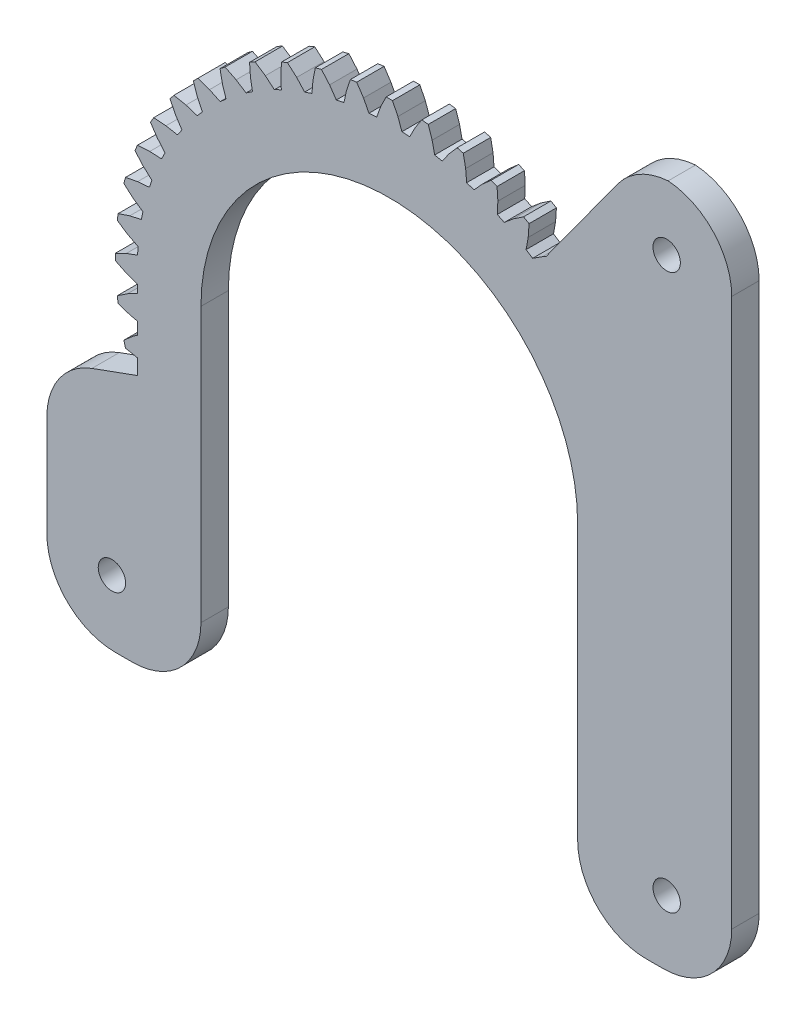
SolidWorks part; units mm, degrees
material "Delrin 2700 NC010, Low Viscosity Acetal Copolymer (SS)"
ref_plane "Front Plane" through (0, 0, 0) normal (0, 0, 1) x (1, 0, 0)
ref_plane "Top Plane" through (0, 0, 0) normal (0, 1, 0) x (1, 0, 0)
ref_plane "Right Plane" through (0, 0, 0) normal (1, 0, 0) x (0, 0, -1)
sketch "Sketch1" plane through (0, 0, 0) normal (0, 0, 1) x (1, 0, 0)
  line L0 (83.8835, 67.191) -> (85.5092, 66.6061)
  line L1 (85.5092, 66.6061) -> (87.1271, 65.8138)
  line L2 (87.1271, 65.8138) -> (87.1271, 64.8854)
  line L3 (87.1271, 64.8854) -> (85.5092, 64.0931)
  line L4 (85.5092, 64.0931) -> (83.8835, 63.5083)
  line L5 (83.8835, 63.5083) -> (83.8095, 62.3776)
  line L6 (83.8095, 62.3776) -> (85.3448, 61.5855)
  line L7 (85.3448, 61.5855) -> (86.8456, 60.5888)
  line L8 (86.8456, 60.5888) -> (86.7243, 59.6683)
  line L9 (86.7243, 59.6683) -> (85.0168, 59.094)
  line L10 (85.0168, 59.094) -> (83.3288, 58.7263)
  line L11 (83.3288, 58.7263) -> (83.1077, 57.615)
  line L12 (83.1077, 57.615) -> (84.5266, 56.6293)
  line L13 (84.5266, 56.6293) -> (85.8844, 55.4453)
  line L14 (85.8844, 55.4453) -> (85.6441, 54.5485)
  line L15 (85.6441, 54.5485) -> (83.8761, 54.202)
  line L16 (83.8761, 54.202) -> (82.1545, 54.0577)
  line L17 (82.1545, 54.0577) -> (81.7903, 52.9848)
  line L18 (81.7903, 52.9848) -> (83.0684, 51.8222)
  line L19 (83.0684, 51.8222) -> (84.26, 50.4711)
  line L20 (84.26, 50.4711) -> (83.9048, 49.6134)
  line L21 (83.9048, 49.6134) -> (82.1066, 49.5006)
  line L22 (82.1066, 49.5006) -> (80.3809, 49.5823)
  line L23 (80.3809, 49.5823) -> (79.8799, 48.5661)
  line L24 (79.8799, 48.5661) -> (80.9952, 47.2468)
  line L25 (80.9952, 47.2468) -> (82.0003, 45.7516)
  line L26 (82.0003, 45.7516) -> (81.5361, 44.9476)
  line L27 (81.5361, 44.9476) -> (79.7387, 45.0704)
  line L28 (79.7387, 45.0704) -> (78.0384, 45.3766)
  line L29 (78.0384, 45.3766) -> (77.4089, 44.4346)
  line L30 (77.4089, 44.4346) -> (78.3426, 42.9809)
  line L31 (78.3426, 42.9809) -> (79.1439, 41.3674)
  line L32 (79.1439, 41.3674) -> (78.5788, 40.6309)
  line L33 (78.5788, 40.6309) -> (76.8128, 40.9873)
  line L34 (76.8128, 40.9873) -> (75.167, 41.5128)
  line L35 (75.167, 41.5128) -> (74.4199, 40.6609)
  line L36 (74.4199, 40.6609) -> (75.1558, 39.0979)
  line L37 (75.1558, 39.0979) -> (75.7397, 37.3936)
  line L38 (75.7397, 37.3936) -> (75.0832, 36.737)
  line L39 (75.0832, 36.737) -> (73.3788, 37.3209)
  line L40 (73.3788, 37.3209) -> (71.8158, 38.0569)
  line L41 (71.8158, 38.0569) -> (70.9639, 37.3097)
  line L42 (70.9639, 37.3097) -> (71.4895, 35.6639)
  line L43 (71.4895, 35.6639) -> (71.8459, 33.898)
  line L44 (71.8459, 33.898) -> (71.1093, 33.3328)
  line L45 (71.1093, 33.3328) -> (69.4958, 34.1341)
  line L46 (69.4958, 34.1341) -> (68.0421, 35.0679)
  line L47 (68.0421, 35.0679) -> (67.1001, 34.4384)
  line L48 (67.1001, 34.4384) -> (67.4064, 32.738)
  line L49 (67.4064, 32.738) -> (67.5292, 30.9407)
  line L50 (67.5292, 30.9407) -> (66.7251, 30.4764)
  line L51 (66.7251, 30.4764) -> (65.23, 31.4815)
  line L52 (65.23, 31.4815) -> (63.9107, 32.5969)
  line L53 (63.9107, 32.5969) -> (62.8945, 32.0958)
  line L54 (62.8945, 32.0958) -> (62.9762, 30.3701)
  line L55 (62.9762, 30.3701) -> (62.8633, 28.572)
  line L56 (62.8633, 28.572) -> (62.0056, 28.2167)
  line L57 (62.0056, 28.2167) -> (60.6545, 29.4083)
  line L58 (60.6545, 29.4083) -> (59.4919, 30.6864)
  line L59 (59.4919, 30.6864) -> (58.419, 30.3222)
  line L60 (58.419, 30.3222) -> (58.2748, 28.6006)
  line L61 (58.2748, 28.6006) -> (57.9283, 26.8327)
  line L62 (57.9283, 26.8327) -> (57.0315, 26.5924)
  line L63 (57.0315, 26.5924) -> (55.8474, 27.9502)
  line L64 (55.8474, 27.9502) -> (54.8618, 29.369)
  line L65 (54.8618, 29.369) -> (53.7504, 29.1479)
  line L66 (53.7504, 29.1479) -> (53.3827, 27.4599)
  line L67 (53.3827, 27.4599) -> (52.8084, 25.7524)
  line L68 (52.8084, 25.7524) -> (51.888, 25.6311)
  line L69 (51.888, 25.6311) -> (50.8913, 27.1319)
  line L70 (50.8913, 27.1319) -> (50.0992, 28.6672)
  line L71 (50.0992, 28.6672) -> (48.9685, 28.5932)
  line L72 (48.9685, 28.5932) -> (48.3836, 26.9675)
  line L73 (48.3836, 26.9675) -> (47.5914, 25.3496)
  line L74 (47.5914, 25.3496) -> (46.6629, 25.3496)
  line L75 (46.6629, 25.3496) -> (45.8707, 26.9675)
  line L76 (45.8707, 26.9675) -> (45.2858, 28.5932)
  line L77 (45.2858, 28.5932) -> (44.1551, 28.6672)
  line L78 (44.1551, 28.6672) -> (43.363, 27.1319)
  line L79 (43.363, 27.1319) -> (42.3663, 25.6311)
  line L80 (42.3663, 25.6311) -> (41.4459, 25.7524)
  line L81 (41.4459, 25.7524) -> (40.8715, 27.4599)
  line L82 (40.8715, 27.4599) -> (40.5038, 29.1479)
  line L83 (40.5038, 29.1479) -> (39.3925, 29.369)
  line L84 (39.3925, 29.369) -> (38.4068, 27.9502)
  line L85 (38.4068, 27.9502) -> (37.2228, 26.5924)
  line L86 (37.2228, 26.5924) -> (36.326, 26.8327)
  line L87 (36.326, 26.8327) -> (35.9795, 28.6006)
  line L88 (35.9795, 28.6006) -> (35.8352, 30.3222)
  line L89 (35.8352, 30.3222) -> (34.7624, 30.6864)
  line L90 (34.7624, 30.6864) -> (33.5998, 29.4083)
  line L91 (33.5998, 29.4083) -> (32.2487, 28.2167)
  line L92 (32.2487, 28.2167) -> (31.3909, 28.572)
  line L93 (31.3909, 28.572) -> (31.2781, 30.3701)
  line L94 (31.2781, 30.3701) -> (31.3598, 32.0958)
  line L95 (31.3598, 32.0958) -> (30.3436, 32.5969)
  line L96 (30.3436, 32.5969) -> (29.0243, 31.4815)
  line L97 (29.0243, 31.4815) -> (27.5292, 30.4764)
  line L98 (27.5292, 30.4764) -> (26.7251, 30.9407)
  line L99 (26.7251, 30.9407) -> (26.8479, 32.738)
  line L100 (26.8479, 32.738) -> (27.1541, 34.4384)
  line L101 (27.1541, 34.4384) -> (26.2121, 35.0679)
  line L102 (26.2121, 35.0679) -> (24.7585, 34.1341)
  line L103 (24.7585, 34.1341) -> (23.1449, 33.3328)
  line L104 (23.1449, 33.3328) -> (22.4084, 33.898)
  line L105 (22.4084, 33.898) -> (22.7648, 35.6639)
  line L106 (22.7648, 35.6639) -> (23.2904, 37.3097)
  line L107 (23.2904, 37.3097) -> (22.4384, 38.0569)
  line L108 (22.4384, 38.0569) -> (20.8754, 37.3209)
  line L109 (20.8754, 37.3209) -> (19.1711, 36.737)
  line L110 (19.1711, 36.737) -> (18.5146, 37.3936)
  line L111 (18.5146, 37.3936) -> (19.0984, 39.0979)
  line L112 (19.0984, 39.0979) -> (19.8344, 40.6609)
  line L113 (19.8344, 40.6609) -> (19.0872, 41.5128)
  line L114 (19.0872, 41.5128) -> (17.4414, 40.9873)
  line L115 (17.4414, 40.9873) -> (15.6755, 40.6309)
  line L116 (15.6755, 40.6309) -> (15.1103, 41.3674)
  line L117 (15.1103, 41.3674) -> (15.9116, 42.9809)
  line L118 (15.9116, 42.9809) -> (16.8454, 44.4346)
  line L119 (16.8454, 44.4346) -> (16.2159, 45.3766)
  line L120 (16.2159, 45.3766) -> (14.5155, 45.0704)
  line L121 (14.5155, 45.0704) -> (12.7182, 44.9476)
  line L122 (12.7182, 44.9476) -> (12.2539, 45.7516)
  line L123 (12.2539, 45.7516) -> (13.2591, 47.2468)
  line L124 (13.2591, 47.2468) -> (14.3744, 48.5661)
  line L125 (14.3744, 48.5661) -> (13.8733, 49.5823)
  line L126 (13.8733, 49.5823) -> (12.1476, 49.5006)
  line L127 (12.1476, 49.5006) -> (10.3495, 49.6134)
  line L128 (10.3495, 49.6134) -> (9.9942, 50.4711)
  line L129 (9.9942, 50.4711) -> (11.1858, 51.8222)
  line L130 (11.1858, 51.8222) -> (12.4639, 52.9848)
  line L131 (12.4639, 52.9848) -> (12.0997, 54.0577)
  line L132 (12.0997, 54.0577) -> (10.3781, 54.202)
  line L133 (10.3781, 54.202) -> (8.6102, 54.5485)
  line L134 (8.6102, 54.5485) -> (8.3699, 55.4453)
  line L135 (8.3699, 55.4453) -> (9.7277, 56.6293)
  line L136 (9.7277, 56.6293) -> (11.1465, 57.615)
  line L137 (11.1465, 57.615) -> (10.9255, 58.7263)
  line L138 (10.9255, 58.7263) -> (9.2374, 59.094)
  line L139 (9.2374, 59.094) -> (7.5299, 59.6683)
  line L140 (7.5299, 59.6683) -> (7.4086, 60.5888)
  line L141 (7.4086, 60.5888) -> (8.9094, 61.5855)
  line L142 (8.9094, 61.5855) -> (10.4448, 62.3776)
  line L143 (10.4448, 62.3776) -> (10.3707, 63.5083)
  line L144 (10.3707, 63.5083) -> (8.745, 64.0931)
  line L145 (8.745, 64.0931) -> (7.1271, 64.8854)
  line L146 (7.1271, 64.8854) -> (7.1271, 65.8138)
  line L147 (7.1271, 65.8138) -> (8.745, 66.6061)
  line L148 (8.745, 66.6061) -> (10.3707, 67.191)
  line L149 (10.3707, 67.191) -> (10.4448, 68.3216)
  line L150 (10.4448, 68.3216) -> (8.9094, 69.1138)
  line L151 (8.9094, 69.1138) -> (7.4086, 70.1105)
  line L152 (7.4086, 70.1105) -> (7.5299, 71.0309)
  line L153 (7.5299, 71.0309) -> (9.2374, 71.6052)
  line L154 (9.2374, 71.6052) -> (10.9255, 71.9729)
  line L155 (10.9255, 71.9729) -> (11.1465, 73.0842)
  line L156 (11.1465, 73.0842) -> (9.7277, 74.0699)
  line L157 (9.7277, 74.0699) -> (8.3699, 75.254)
  line L158 (8.3699, 75.254) -> (8.6102, 76.1508)
  line L159 (8.6102, 76.1508) -> (10.3781, 76.4973)
  line L160 (10.3781, 76.4973) -> (12.0997, 76.6415)
  line L161 (12.0997, 76.6415) -> (12.4639, 77.7144)
  line L162 (12.4639, 77.7144) -> (11.1858, 78.877)
  line L163 (11.1858, 78.877) -> (9.9942, 80.2281)
  line L164 (9.9942, 80.2281) -> (10.3495, 81.0858)
  line L165 (10.3495, 81.0858) -> (12.1476, 81.1987)
  line L166 (12.1476, 81.1987) -> (13.8733, 81.117)
  line L167 (13.8733, 81.117) -> (14.3744, 82.1332)
  line L168 (14.3744, 82.1332) -> (13.2591, 83.4525)
  line L169 (13.2591, 83.4525) -> (12.2539, 84.9476)
  line L170 (12.2539, 84.9476) -> (12.7182, 85.7516)
  line L171 (12.7182, 85.7516) -> (14.5155, 85.6289)
  line L172 (14.5155, 85.6289) -> (16.2159, 85.3226)
  line L173 (16.2159, 85.3226) -> (16.8454, 86.2646)
  line L174 (16.8454, 86.2646) -> (15.9116, 87.7183)
  line L175 (15.9116, 87.7183) -> (15.1103, 89.3318)
  line L176 (15.1103, 89.3318) -> (15.6755, 90.0684)
  line L177 (15.6755, 90.0684) -> (17.4414, 89.712)
  line L178 (17.4414, 89.712) -> (19.0872, 89.1864)
  line L179 (19.0872, 89.1864) -> (19.8344, 90.0383)
  line L180 (19.8344, 90.0383) -> (19.0984, 91.6013)
  line L181 (19.0984, 91.6013) -> (18.5146, 93.3057)
  line L182 (18.5146, 93.3057) -> (19.1711, 93.9622)
  line L183 (19.1711, 93.9622) -> (20.8754, 93.3783)
  line L184 (20.8754, 93.3783) -> (22.4384, 92.6424)
  line L185 (22.4384, 92.6424) -> (23.2904, 93.3895)
  line L186 (23.2904, 93.3895) -> (22.7648, 95.0353)
  line L187 (22.7648, 95.0353) -> (22.4084, 96.8013)
  line L188 (22.4084, 96.8013) -> (23.1449, 97.3664)
  line L189 (23.1449, 97.3664) -> (24.7585, 96.5651)
  line L190 (24.7585, 96.5651) -> (26.2121, 95.6314)
  line L191 (26.2121, 95.6314) -> (27.1541, 96.2609)
  line L192 (27.1541, 96.2609) -> (26.8479, 97.9612)
  line L193 (26.8479, 97.9612) -> (26.7251, 99.7586)
  line L194 (26.7251, 99.7586) -> (27.5292, 100.2228)
  line L195 (27.5292, 100.2228) -> (29.0243, 99.2177)
  line L196 (29.0243, 99.2177) -> (30.3436, 98.1023)
  line L197 (30.3436, 98.1023) -> (31.3598, 98.6034)
  line L198 (31.3598, 98.6034) -> (31.2781, 100.3291)
  line L199 (31.2781, 100.3291) -> (31.3909, 102.1272)
  line L200 (31.3909, 102.1272) -> (32.2487, 102.4825)
  line L201 (32.2487, 102.4825) -> (33.5998, 101.2909)
  line L202 (33.5998, 101.2909) -> (34.7624, 100.0128)
  line L203 (34.7624, 100.0128) -> (35.8352, 100.377)
  line L204 (35.8352, 100.377) -> (35.9795, 102.0986)
  line L205 (35.9795, 102.0986) -> (36.326, 103.8666)
  line L206 (36.326, 103.8666) -> (37.2228, 104.1068)
  line L207 (37.2228, 104.1068) -> (38.4068, 102.7491)
  line L208 (38.4068, 102.7491) -> (39.3925, 101.3302)
  line L209 (39.3925, 101.3302) -> (40.5038, 101.5513)
  line L210 (40.5038, 101.5513) -> (40.8715, 103.2393)
  line L211 (40.8715, 103.2393) -> (41.4459, 104.9468)
  line L212 (41.4459, 104.9468) -> (42.3663, 105.0681)
  line L213 (42.3663, 105.0681) -> (43.363, 103.5673)
  line L214 (43.363, 103.5673) -> (44.1551, 102.032)
  line L215 (44.1551, 102.032) -> (45.2858, 102.106)
  line L216 (45.2858, 102.106) -> (45.8707, 103.7317)
  line L217 (45.8707, 103.7317) -> (46.6629, 105.3496)
  line L218 (46.6629, 105.3496) -> (47.5914, 105.3496)
  line L219 (47.5914, 105.3496) -> (48.3836, 103.7317)
  line L220 (48.3836, 103.7317) -> (48.9685, 102.106)
  line L221 (48.9685, 102.106) -> (50.0992, 102.032)
  line L222 (50.0992, 102.032) -> (50.8913, 103.5673)
  line L223 (50.8913, 103.5673) -> (51.888, 105.0681)
  line L224 (51.888, 105.0681) -> (52.8084, 104.9468)
  line L225 (52.8084, 104.9468) -> (53.3827, 103.2393)
  line L226 (53.3827, 103.2393) -> (53.7504, 101.5513)
  line L227 (53.7504, 101.5513) -> (54.8618, 101.3302)
  line L228 (54.8618, 101.3302) -> (55.8474, 102.7491)
  line L229 (55.8474, 102.7491) -> (57.0315, 104.1068)
  line L230 (57.0315, 104.1068) -> (57.9283, 103.8666)
  line L231 (57.9283, 103.8666) -> (58.2748, 102.0986)
  line L232 (58.2748, 102.0986) -> (58.419, 100.377)
  line L233 (58.419, 100.377) -> (59.4919, 100.0128)
  line L234 (59.4919, 100.0128) -> (60.6545, 101.2909)
  line L235 (60.6545, 101.2909) -> (62.0056, 102.4825)
  line L236 (62.0056, 102.4825) -> (62.8633, 102.1272)
  line L237 (62.8633, 102.1272) -> (62.9762, 100.3291)
  line L238 (62.9762, 100.3291) -> (62.8945, 98.6034)
  line L239 (62.8945, 98.6034) -> (63.9107, 98.1023)
  line L240 (63.9107, 98.1023) -> (65.23, 99.2177)
  line L241 (65.23, 99.2177) -> (66.7251, 100.2228)
  line L242 (66.7251, 100.2228) -> (67.5292, 99.7586)
  line L243 (67.5292, 99.7586) -> (67.4064, 97.9612)
  line L244 (67.4064, 97.9612) -> (67.1001, 96.2609)
  line L245 (67.1001, 96.2609) -> (68.0421, 95.6314)
  line L246 (68.0421, 95.6314) -> (69.4958, 96.5651)
  line L247 (69.4958, 96.5651) -> (71.1093, 97.3664)
  line L248 (71.1093, 97.3664) -> (71.8459, 96.8013)
  line L249 (71.8459, 96.8013) -> (71.4895, 95.0353)
  line L250 (71.4895, 95.0353) -> (70.9639, 93.3895)
  line L251 (70.9639, 93.3895) -> (71.8158, 92.6424)
  line L252 (71.8158, 92.6424) -> (73.3788, 93.3783)
  line L253 (73.3788, 93.3783) -> (75.0832, 93.9622)
  line L254 (75.0832, 93.9622) -> (75.7397, 93.3057)
  line L255 (75.7397, 93.3057) -> (75.1558, 91.6013)
  line L256 (75.1558, 91.6013) -> (74.4199, 90.0383)
  line L257 (74.4199, 90.0383) -> (75.167, 89.1864)
  line L258 (75.167, 89.1864) -> (76.8128, 89.712)
  line L259 (76.8128, 89.712) -> (78.5788, 90.0684)
  line L260 (78.5788, 90.0684) -> (79.1439, 89.3318)
  line L261 (79.1439, 89.3318) -> (78.3426, 87.7183)
  line L262 (78.3426, 87.7183) -> (77.4089, 86.2646)
  line L263 (77.4089, 86.2646) -> (78.0384, 85.3226)
  line L264 (78.0384, 85.3226) -> (79.7387, 85.6289)
  line L265 (79.7387, 85.6289) -> (81.5361, 85.7516)
  line L266 (81.5361, 85.7516) -> (82.0003, 84.9476)
  line L267 (82.0003, 84.9476) -> (80.9952, 83.4525)
  line L268 (80.9952, 83.4525) -> (79.8799, 82.1332)
  line L269 (79.8799, 82.1332) -> (80.3809, 81.117)
  line L270 (80.3809, 81.117) -> (82.1066, 81.1987)
  line L271 (82.1066, 81.1987) -> (83.9048, 81.0858)
  line L272 (83.9048, 81.0858) -> (84.26, 80.2281)
  line L273 (84.26, 80.2281) -> (83.0684, 78.877)
  line L274 (83.0684, 78.877) -> (81.7903, 77.7144)
  line L275 (81.7903, 77.7144) -> (82.1545, 76.6415)
  line L276 (82.1545, 76.6415) -> (83.8761, 76.4973)
  line L277 (83.8761, 76.4973) -> (85.6441, 76.1508)
  line L278 (85.6441, 76.1508) -> (85.8844, 75.254)
  line L279 (85.8844, 75.254) -> (84.5266, 74.0699)
  line L280 (84.5266, 74.0699) -> (83.1077, 73.0842)
  line L281 (83.1077, 73.0842) -> (83.3288, 71.9729)
  line L282 (83.3288, 71.9729) -> (85.0168, 71.6052)
  line L283 (85.0168, 71.6052) -> (86.7243, 71.0309)
  line L284 (86.7243, 71.0309) -> (86.8456, 70.1105)
  line L285 (86.8456, 70.1105) -> (85.3448, 69.1138)
  line L286 (85.3448, 69.1138) -> (83.8095, 68.3216)
  line L287 (83.8095, 68.3216) -> (83.8835, 67.191)
  line L288 (47.1271, 105.3496) -> (47.1271, 25.3496) construction
  line L289 (7.1271, 65.3496) -> (87.1271, 65.3496) construction
  point P292 (47.1271, 65.3496)
sketch "Sketch2" plane through (0, 0, 0) normal (0, 0, 1) x (1, 0, 0)
  line L0 (-2.8729, 47.1511) -> (10.3271, 51.9555)
  line L1 (47.1271, 65.3496) -> (97.1271, 65.3496) construction
  line L2 (47.1271, 65.3496) -> (47.1271, 15.3496) construction
  line L3 (47.1271, 15.3496) -> (97.1271, 15.3496)
  line L4 (97.1271, 65.3496) -> (97.1271, 15.3496)
  line L5 (47.1271, 65.3496) -> (83.4543, 115.3496)
  line L6 (47.1271, 65.3496) -> (47.1271, 15.3496) construction
  line L7 (47.1271, 15.3496) -> (-2.8729, 15.3496)
  line L8 (-2.8729, 47.1511) -> (-2.8729, 15.3496)
  line L9 (47.1271, 65.3496) -> (97.1271, 65.3496) construction
  line L10 (7.1271, 65.3496) -> (87.1271, 65.3496) construction
  line L11 (83.4543, 115.3496) -> (97.1271, 115.3496)
  line L12 (97.1271, 65.3496) -> (97.1271, 115.3496)
  line L13 (47.1271, 105.3496) -> (47.1271, 25.3496) construction
  line L14 (10.3271, 51.9555) -> (10.3271, 65.3496)
  line L15 (10.3271, 65.3496) -> (47.1271, 65.3496)
  line L16 (10.3271, 51.9555) -> (47.1271, 65.3496) construction
  dimension "D1" = 100
  dimension "D2" = 100
  dimension "D3" = 20
  dimension "D4" = 36
  dimension "D5" = 13.2
sketch "Sketch3" plane through (0, 0, 0) normal (0, 0, 1) x (1, 0, 0)
  line L0 (6.6271, 24.8496) -> (-2.8729, 24.8496) construction
  line L1 (-2.8729, 47.1511) -> (-2.8729, 15.3496) construction
  line L2 (6.6271, 24.8496) -> (6.6271, 15.3496) construction
  line L3 (47.1271, 15.3496) -> (-2.8729, 15.3496) construction
  line L4 (47.1271, 65.3496) -> (47.1271, 15.3496) construction
  line L5 (7.1271, 65.3496) -> (87.1271, 65.3496) construction
  line L6 (47.1271, 65.3496) -> (97.1271, 65.3496) construction
  circle A0 centre (6.6271, 24.8496) radius 2
  circle A1 centre (87.6271, 24.8496) radius 2
  circle A2 centre (87.6271, 105.8496) radius 2
  dimension "D1" = 4
  dimension "D2" = 81
sketch "Sketch4" plane through (0, 0, 0) normal (0, 0, 1) x (1, 0, 0)
  circle A0 centre (47.1271, 65.3496) radius 27.5
  dimension "D1" = 55
extrude "Boss-Extrude1" add sketch "Sketch1" along normal blind 4
extrude "Boss-Extrude2" add sketch "Sketch2" along normal blind 4
extrude "Cut-Extrude1" cut sketch "Sketch3" along normal up to next
extrude "Cut-Extrude2" cut sketch "Sketch4" along normal up to next
sketch "Sketch5" plane through (0, 0, 0) normal (0, 0, 1) x (1, 0, 0)
  line L0 (74.6271, 65.3496) -> (74.6271, 15.3496)
  line L1 (-2.8729, 15.3496) -> (97.1271, 15.3496) construction
  line L2 (19.6271, 65.3496) -> (19.6271, 15.3496)
  line L3 (19.6271, 15.3496) -> (74.6271, 15.3496)
  line L4 (19.6271, 65.3496) -> (74.6271, 65.3496)
  circle A0 centre (47.1271, 65.3496) radius 27.5 construction
  dimension "D1" = 55
extrude "Cut-Extrude3" cut sketch "Sketch5" along normal up to next
fillet "Fillet1" radius 10 7 edges at (83.4543, 115.3496, 2) (97.1271, 115.3496, 2) (97.1271, 15.3496, 2) (74.6271, 15.3496, 2) (19.6271, 15.3496, 2) (-2.8729, 15.3496, 2) (-2.8729, 47.1511, 2)
